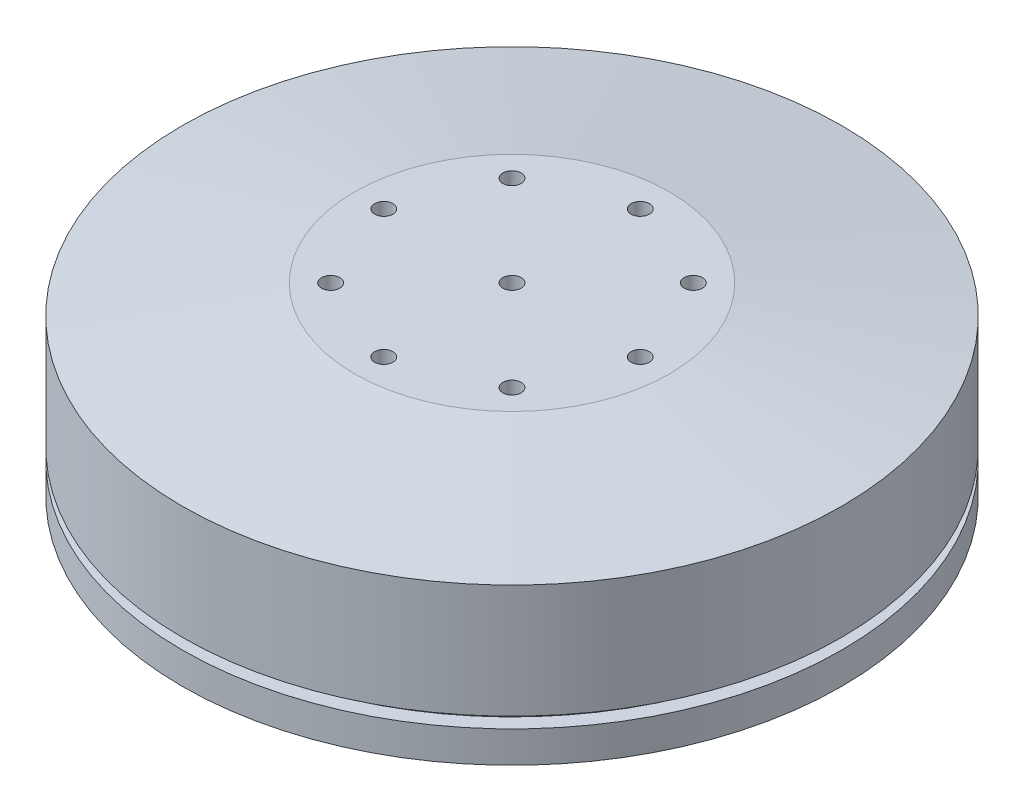
SolidWorks part; units mm, degrees
ref_plane "Спереди" through (0, 0, 0) normal (0, 0, 1) x (1, 0, 0)
ref_plane "Сверху" through (0, 0, 0) normal (0, 1, 0) x (1, 0, 0)
ref_plane "Справа" through (0, 0, 0) normal (1, 0, 0) x (0, 0, -1)
ref_axis "Axis1" through (0, 0, 0) along (0, 1, 0)
sketch "Sketch1" plane through (0, 0, 0) normal (0, 0, 1) x (1, 0, 0)
  line L0 (0, 0) -> (0, -30873.715) construction
  line L1 (0, 0) -> (0, 33.5)
  line L2 (0, 33.5) -> (-21.5, 33.5)
  line L3 (-21.5, 33.5) -> (-45, 29.6)
  line L4 (-45, 29.6) -> (-45, 14.1)
  line L5 (-45, 14.1) -> (-43, 14.1)
  line L6 (-43, 14.1) -> (-43, 12.6)
  line L7 (-43, 12.6) -> (-45, 12.6)
  line L8 (-45, 12.6) -> (-45, 8.3)
  line L9 (-45, 8.3) -> (-26.5, 5.6)
  line L10 (-26.5, 5.6) -> (-26.5, 0)
  line L11 (-26.5, 0) -> (0, 0)
  dimension "D1" = 33.5
  dimension "D2" = 43
  dimension "D3" = 90
  dimension "D4" = 3.9
  dimension "D5" = 1.5
  dimension "D6" = 2
  dimension "D7" = 4.3
  dimension "D8" = 5.6
  dimension "D9" = 2.7
  dimension "D10" = 53
revolve "Revolve1" add sketch "Sketch1" angle 360 about L0
hole_wizard "Tap Drill for M3x0.5 Tap1" positions "Sketch3" profile "Sketch4" hole size "M3x0.5" standard "ANSI Metric"
sketch "Sketch3" plane through (0, 33.5, 0) normal (0, 1, 0) x (1, 0, 0)
  point P0 (0, 17.5)
  point P12 (12.3744, 12.3744)
  point P13 (17.5, 0)
  point P14 (12.3744, -12.3744)
  point P15 (0, -17.5)
  point P16 (-12.3744, -12.3744)
  point P17 (-17.5, 0)
  point P18 (-12.3744, 12.3744)
  point P19 (0, 0)
  dimension "D1" = 17.5
  dimension "D2" = 8
sketch "Sketch4" plane through (0, 33.5, -17.5) normal (1, 0, 0) x (0, 0, 1)
  line L0 (0, 0) -> (0, 6.7511)
  line L1 (0, 6.7511) -> (1.25, 6)
  line L2 (1.25, 6) -> (1.25, 0)
  line L5 (1.25, 0) -> (0, 0)
  line L10 (0, 6.7511) -> (-1.25, 6) construction
  line L11 (0, -6.35) -> (0, 107.95) construction
  dimension "Hole Dia." = 2.5
  dimension "Hole Depth" = 6
  dimension "Drill Angle" = 118
hole_wizard "Tap Drill for M3x0.5 Tap2" positions "Sketch5" profile "Sketch6" hole size "M3x0.5" standard "ANSI Metric"
sketch "Sketch5" plane through (0, 0, 0) normal (0, -1, 0) x (-1, 0, 0)
  point P0 (0, 15)
  point P9 (15, 0)
  point P10 (0, -15)
  point P11 (-15, 0)
  point P12 (0, 0)
  dimension "D1" = 15
  dimension "D2" = 4
sketch "Sketch6" plane through (0, 0, -15) normal (1, 0, 0) x (0, 0, -1)
  line L0 (0, 0) -> (0, 6.7511)
  line L1 (0, 6.7511) -> (1.25, 6)
  line L2 (1.25, 6) -> (1.25, 0)
  line L5 (1.25, 0) -> (0, 0)
  line L10 (0, 6.7511) -> (-1.25, 6) construction
  line L11 (0, -6.35) -> (0, 107.95) construction
  dimension "Hole Dia." = 2.5
  dimension "Hole Depth" = 6
  dimension "Drill Angle" = 118
